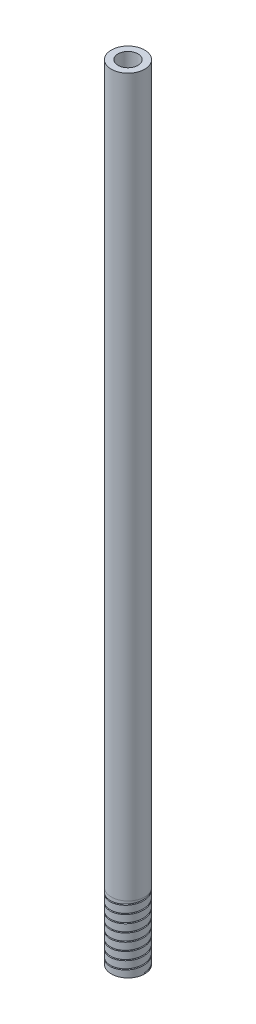
SolidWorks part; units mm, degrees
ref_plane "Front Plane" through (0, 0, 0) normal (0, 0, 1) x (1, 0, 0)
ref_plane "Top Plane" through (0, 0, 0) normal (0, 1, 0) x (1, 0, 0)
ref_plane "Right Plane" through (0, 0, 0) normal (1, 0, 0) x (0, 0, -1)
sketch "Sketch1" plane through (0, 0, 0) normal (0, 1, 0) x (1, 0, 0)
  circle A0 centre (0, 0) radius 25
  dimension "D1" = 50
extrude "Boss-Extrude1" add sketch "Sketch1" along normal blind 100
sketch "Sketch2" plane through (0, 100, 0) normal (0, 1, 0) x (1, 0, 0)
  circle A0 centre (0, 0) radius 25
  dimension "D1" = 50
extrude "Boss-Extrude2" add sketch "Sketch2" along normal blind 1075 separate body
thread "Thread1" pitch 2 method cut profile "Thread Profile1" start angle 0, offset 0, length 100, pitch 12, diameter 50
ref_plane "Plane4" through (25, 0, 0) normal (0, 0, 1) x (1, 0, 0)
sketch "Thread Profile1" plane through (25, 0, 0) normal (0, 0, 1) x (1, 0, 0)
  line L0 (0, 0) -> (0, 2) construction
  line L11 (0, 0) -> (0, 1.75)
  line L12 (0, 1.75) -> (-1.0825, 1.125)
  line L13 (-1.0825, 1.125) -> (-1.0825, 0.625)
  line L15 (-1.0825, 0.625) -> (0, 0)
  line L17 (-1.0825, 0.875) -> (0, 0.875) construction
  point P2 (0, 0)
  dimension "Pitch" = 2
  dimension "Profile_Angle" = 60
  dimension "Profile_Land" = 0.5
  dimension "Profile_Height" = 1.0825
sketch "Sketch5" plane through (0, 1175, 0) normal (0, 1, 0) x (1, 0, 0)
  circle A0 centre (0, 0) radius 15
  dimension "D1" = 30
extrude "Cut-Extrude1" cut sketch "Sketch5" against normal blind 75
